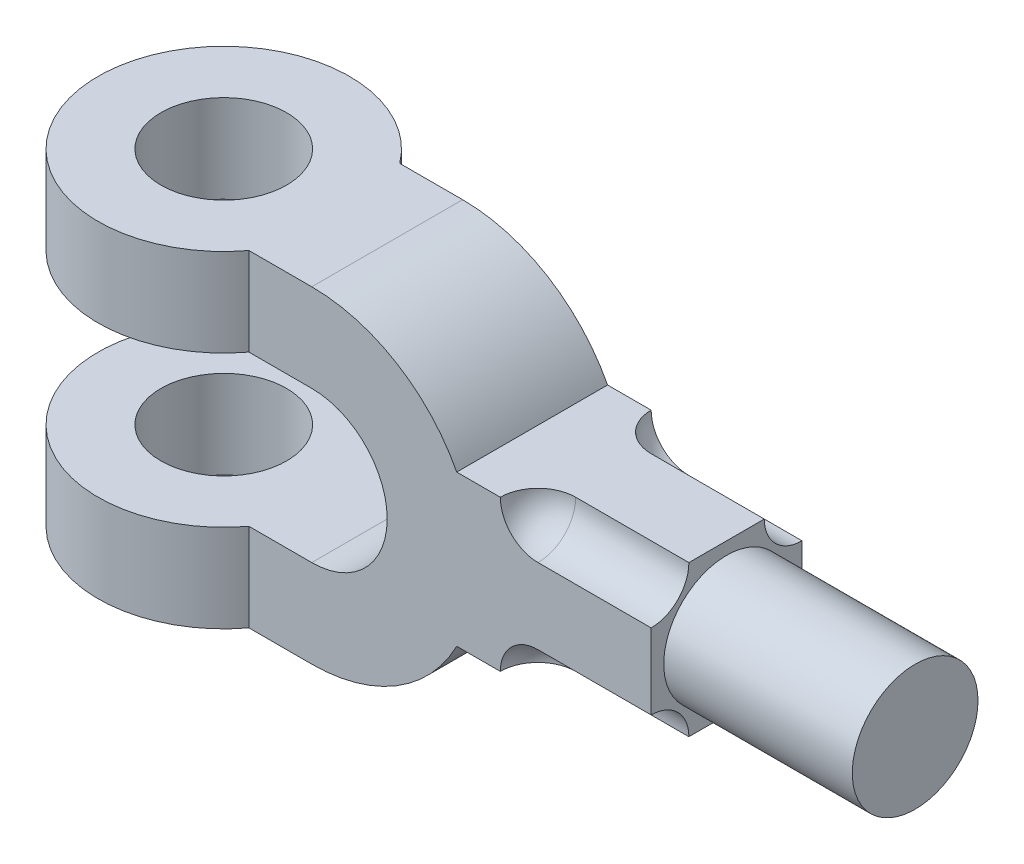
SolidWorks part; units mm, degrees
material "AISI 1020"
ref_plane "Front Plane" through (0, 0, 0) normal (0, 0, 1) x (1, 0, 0)
ref_plane "Top Plane" through (0, 0, 0) normal (0, 1, 0) x (1, 0, 0)
ref_plane "Right Plane" through (0, 0, 0) normal (1, 0, 0) x (0, 0, -1)
sketch "Sketch1" plane through (0, 0, 0) normal (0, 1, 0) x (1, 0, 0)
  circle A0 centre (0, 0) radius 20
  dimension "D1" = 40
extrude "Boss-Extrude1" add sketch "Sketch1" along normal blind 52
sketch "Sketch2" plane through (0, 52, 0) normal (0, 1, 0) x (1, 0, 0)
  circle A0 centre (0, 0) radius 10
  dimension "D1" = 20
extrude "Cut-Extrude1" cut sketch "Sketch2" against normal through all both and the other way through all
sketch "Sketch5" plane through (0, 0, 0) normal (0, 0, 1) x (1, 0, 0)
  line L0 (-210.6336, 26) -> (210.6336, 26) construction
  line L1 (0, 108.8918) -> (0, -56.8918) construction
  line L2 (20, 52) -> (-20, 52) construction
  line L3 (26, 0) -> (16, 0)
  line L4 (16, 52) -> (16, 38)
  line L5 (26, 38) -> (16, 38)
  line L6 (26, 52) -> (16, 52)
  line L7 (49.0651, 38) -> (80, 38)
  line L9 (49.0651, 14) -> (80, 14)
  line L10 (80, 38) -> (80, 14)
  line L11 (62.2613, 14) -> (62.2613, 38) construction
  line L12 (44.5227, 26) -> (80, 26) construction
  line L19 (26, 14) -> (16, 14)
  line L20 (16, 14) -> (16, 0)
  arc A1 (26, 0) -> (49.0651, 14) centre (26, 26) ccw
  arc A2 (49.0651, 38) -> (26, 52) centre (26, 26) ccw
  arc A3 (26, 14) -> (26, 38) centre (26, 26) ccw
  point P3 (0, 26)
  point P7 (0, 26)
  point P13 (62.2613, 26)
  dimension "D2" = 24
  dimension "D3" = 52
  dimension "D1" = 26
  dimension "D4" = 26
  dimension "D5" = 24
  dimension "D6" = 80
  dimension "D7" = 10
extrude "Boss-Extrude8" add sketch "Sketch5" along normal mid plane 24
sketch "Sketch7" plane through (80, 0, 0) normal (1, 0, 0) x (0, 0, -1)
  line L0 (-12, 14) -> (-12, 38) construction
  circle A0 centre (0, 26) radius 10
  dimension "D1" = 20
  dimension "D2" = 12
extrude "Boss-Extrude9" add sketch "Sketch7" along normal blind 30
sketch "Sketch9" plane through (80, 0, 0) normal (1, 0, 0) x (0, 0, -1)
  line L1 (-23.0426, 26) -> (23.0426, 26) construction
  circle A0 centre (-12, 38) radius 6
  circle A1 centre (12, 38) radius 6
  circle A2 centre (12, 14) radius 6
  circle A3 centre (-12, 14) radius 6
  point P10 (0, 26)
  dimension "D1" = 12
  dimension "D2" = 12
extrude "Cut-Extrude2" cut sketch "Sketch9" against normal blind 24 and the other way through all
fillet "Fillet1" radius 6 4 edges at (56, 18.2426, -7.7574) (56, 18.2426, 7.7574) (56, 33.7574, -7.7574) (56, 33.7574, 7.7574)
sketch "Sketch11" plane through (0, 0, 0) normal (0, 0, 1) x (1, 0, 0)
  line L0 (16, 52) -> (-20, 52) construction
  line L1 (-21.1631, 38) -> (21.1631, 38)
  line L2 (-21.1631, 38) -> (-21.1631, 14)
  line L3 (-21.1631, 14) -> (21.1631, 14)
  line L4 (21.1631, 38) -> (21.1631, 14)
  line L5 (0, 14) -> (0, 38) construction
  line L6 (-21.1631, 26) -> (21.1631, 26) construction
  line L7 (-20, 0) -> (16, 0) construction
  point P0 (0, 26)
  dimension "D1" = 14
  dimension "D2" = 14
extrude "Cut-Extrude3" cut sketch "Sketch11" against normal through all both and the other way through all
